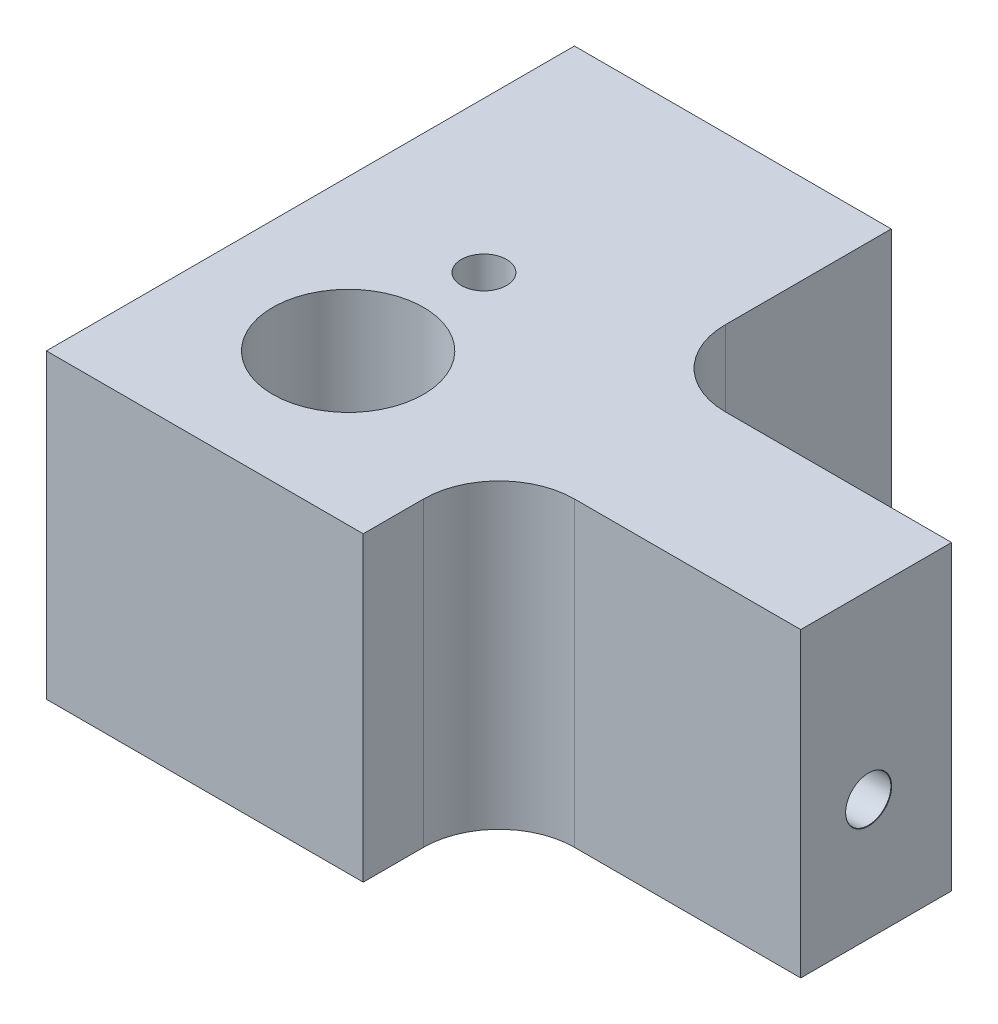
SolidWorks part; units mm, degrees
ref_plane "Front Plane" through (0, 0, 0) normal (0, 0, 1) x (1, 0, 0)
ref_plane "Top Plane" through (0, 0, 0) normal (0, 1, 0) x (1, 0, 0)
ref_plane "Right Plane" through (0, 0, 0) normal (1, 0, 0) x (0, 0, -1)
sketch "Sketch1" plane through (0, 0, 0) normal (0, 1, 0) x (1, 0, 0)
  line L1 (-10.5256, 22.3096) -> (38.4744, 22.3096)
  line L2 (-10.5256, 22.3096) -> (-10.5256, -12.6904)
  line L3 (-10.5256, -12.6904) -> (38.4744, -12.6904)
  line L4 (38.4744, 22.3096) -> (38.4744, -12.6904)
  dimension "D1" = 35
  dimension "D2" = 49
extrude "Boss-Extrude1" add sketch "Sketch1" along normal blind 20
hole_wizard "Ø3.0mm Dowel Hole1" positions "Sketch3" profile "Sketch4" hole size "Ø3.0" standard "ANSI Metric"
sketch "Sketch3" plane through (0, 0, -22.3096) normal (0, 0, -1) x (-1, 0, 0)
  line L0 (-38.4744, 20) -> (-38.4744, 0) construction
  line L3 (-38.4744, 0) -> (10.5256, 0) construction
  point P0 (-7.4744, 4)
  dimension "D1" = 31
  dimension "D2" = 4
sketch "Sketch4" plane through (7.4744, 4, -22.3096) normal (1, 0, 0) x (0, 1, 0)
  line L0 (0, 0) -> (0, 12)
  line L1 (0, 12) -> (1.5, 11.0987)
  line L2 (1.5, 11.0987) -> (1.5, 0.025)
  line L3 (1.5, 0.025) -> (1.525, 0)
  line L5 (1.525, 0) -> (0, 0)
  line L6 (-1.5, 0.025) -> (-1.525, 0) construction
  line L10 (0, 12) -> (-1.5, 11.0987) construction
  line L11 (0, -6.35) -> (0, 107.95) construction
  dimension "Hole Dia." = 3
  dimension "Hole Depth" = 12
  dimension "Near C'Sink Dia." = 3.05
  dimension "Near C'Sink Angle" = 90
  dimension "Drill Angle" = 118
hole_wizard "Ø3.0mm Dowel Hole2" positions "Sketch7" profile "Sketch8" hole size "Ø3.0" standard "ANSI Metric"
sketch "Sketch7" plane through (38.4744, 0, 0) normal (1, 0, 0) x (0, 0, -1)
  line L0 (-12.6904, 0) -> (22.3096, 0) construction
  line L1 (22.3096, 20) -> (22.3096, 0) construction
  point P0 (0.8096, 8)
  dimension "D1" = 8
  dimension "D2" = 21.5
sketch "Sketch8" plane through (38.4744, 8, -0.8096) normal (0, 1, 0) x (0, 0, -1)
  line L0 (0, 0) -> (0, 12.9013)
  line L1 (0, 12.9013) -> (1.5, 12)
  line L2 (1.5, 12) -> (1.5, 0.025)
  line L3 (1.5, 0.025) -> (1.525, 0)
  line L5 (1.525, 0) -> (0, 0)
  line L6 (-1.5, 0.025) -> (-1.525, 0) construction
  line L10 (0, 12.9013) -> (-1.5, 12) construction
  line L11 (0, -6.35) -> (0, 107.95) construction
  dimension "Hole Dia." = 3
  dimension "Hole Depth" = 12
  dimension "Near C'Sink Dia." = 3.05
  dimension "Near C'Sink Angle" = 90
  dimension "Drill Angle" = 118
hole_wizard "Ø3.0mm Dowel Hole3" positions "Sketch9" profile "Sketch10" hole size "Ø3.0" standard "ANSI Metric" end condition through all
sketch "Sketch9" plane through (0, 0, 0) normal (0, -1, 0) x (-1, 0, 0)
  line L1 (-38.4744, 22.3096) -> (10.5256, 22.3096) construction
  line L3 (-38.4744, -12.6904) -> (-38.4744, 22.3096) construction
  point P0 (-7.4744, 6.3096)
  dimension "D1" = 31
  dimension "D2" = 16
sketch "Sketch10" plane through (7.4744, 0, -6.3096) normal (1, 0, 0) x (0, 0, -1)
  line L0 (0, 0) -> (0, 20)
  line L1 (0, 20) -> (1.5, 20)
  line L2 (1.5, 20) -> (1.5, 0.025)
  line L3 (1.5, 0.025) -> (1.525, 0)
  line L5 (1.525, 0) -> (0, 0)
  line L6 (-1.5, 0.025) -> (-1.525, 0) construction
  line L11 (0, -6.35) -> (0, 107.95) construction
  dimension "Thru Hole Dia." = 3
  dimension "Thru Hole Depth" = 20
  dimension "Near C'Sink Dia." = 3.05
  dimension "Near C'Sink Angle" = 90
sketch "Sketch14" plane through (0, 20, 0) normal (0, 1, 0) x (1, 0, 0)
  line L0 (-10.5256, -12.6904) -> (38.4744, -12.6904) construction
  line L1 (-10.5256, 22.3096) -> (-2.5256, 22.3096)
  line L2 (-10.5256, 22.3096) -> (-10.5256, -12.6904)
  line L3 (-10.5256, -12.6904) -> (-2.5256, -12.6904)
  line L4 (-2.5256, 22.3096) -> (-2.5256, -12.6904)
  line L7 (18.4744, 22.3096) -> (38.4744, 22.3096)
  line L8 (18.4744, 22.3096) -> (18.4744, 6.3096)
  line L9 (18.4744, 6.3096) -> (38.4744, 6.3096)
  line L10 (38.4744, 22.3096) -> (38.4744, 6.3096)
  line L13 (38.4744, -12.6904) -> (18.4744, -12.6904)
  line L14 (38.4744, -12.6904) -> (38.4744, -3.6904)
  line L15 (38.4744, -3.6904) -> (18.4744, -3.6904)
  line L16 (18.4744, -12.6904) -> (18.4744, -3.6904)
  dimension "D1" = 0
  dimension "D2" = 8
  dimension "D3" = 9
  dimension "D4" = 20
  dimension "D5" = 10
  dimension "D6" = 20
extrude "Cut-Extrude3" cut sketch "Sketch14" against normal blind 28
sketch "Sketch15" plane through (0, 20, 0) normal (0, 1, 0) x (1, 0, 0)
  line L0 (18.4744, 22.3096) -> (-2.5256, 22.3096) construction
  circle A0 centre (7.4744, -2.6904) radius 5
  dimension "D1" = 25
extrude "Cut-Extrude4" cut sketch "Sketch15" against normal blind 30
fillet "Fillet1" radius 5 2 edges at (18.4744, 10, 3.6904) (18.4744, 10, -6.3096)
